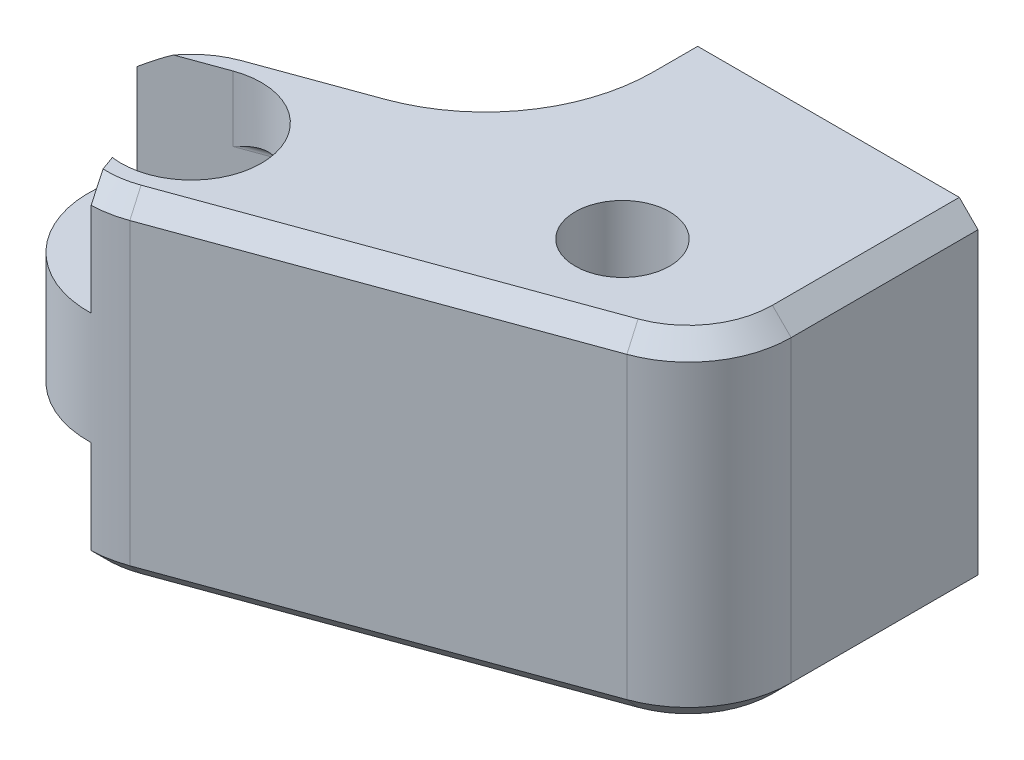
SolidWorks part; units mm, degrees
ref_plane "前视基准面" through (0, 0, 0) normal (0, 0, 1) x (1, 0, 0)
ref_plane "上视基准面" through (0, 0, 0) normal (0, 1, 0) x (1, 0, 0)
ref_plane "右视基准面" through (0, 0, 0) normal (1, 0, 0) x (0, 0, -1)
other "Configuration Table"
ref_plane "基准面1" through (0, 18, 0) normal (0, 1, 0) x (1, 0, 0)
sketch "草图1" plane through (0, 18, 0) normal (0, 1, 0) x (1, 0, 0)
  line L0 (-17.6189, -12.2657) -> (21.6618, 2.0313)
  line L1 (21.6618, 2.0313) -> (-10.5, 2.0313)
  line L2 (-10.5, 2.0313) -> (-21.3811, -1.9291)
  arc A0 (-21.3811, -1.9291) -> (-17.6189, -12.2657) centre (-19.5, -7.0974) ccw
  dimension "D1" = 5.5
  dimension "D2" = 32.1618
  dimension "D3" = 39.2807
  dimension "D4" = 41.1618
extrude "凸台-拉伸1" add sketch "草图1" against normal blind 15
sketch "草图2" plane through (0, 18, 0) normal (0, 1, 0) x (-1, 0, 0)
  line L0 (-21.6618, -2.0313) -> (-5.5, -2.0313)
  line L1 (-5.5, -2.0313) -> (-5.5, 3.8511)
  line L2 (-5.5, 3.8511) -> (-21.6618, -2.0313)
  dimension "D1" = 16.1618
  dimension "D2" = 1.922
  dimension "D3" = 3.9604
extrude "切除-拉伸1" cut sketch "草图2" against normal through all
sketch "草图3" plane through (0, 18, 0) normal (0, 1, 0) x (-1, 0, 0)
  line L0 (20.7826, 3.5736) -> (24.5633, 4.9496)
  line L1 (19.3611, 12.5957) -> (20.0101, 10.8126)
  line L2 (-5.5, -2.0313) -> (-5.5, 3.8511) construction
  line L3 (-5.5, -2.0313) -> (10.5, -2.0313) construction
  arc A0 (20.0101, 10.8126) -> (20.7826, 3.5736) centre (19.5, 7.0974) ccw
  arc A1 (24.5633, 4.9496) -> (19.3611, 12.5957) centre (19.5, 7.0974) ccw
  dimension "D1" = 3.75
  dimension "D2" = 5.5
  dimension "D3" = 24.8611
  dimension "D4" = 25
  dimension "D5" = 25.5101
  dimension "D6" = 26.2826
  dimension "D7" = 5.6049
extrude "切除-拉伸2" cut sketch "草图3" against normal blind 6
ref_plane "基准面2" through (0, 12, 0) normal (0, -1, 0) x (1, 0, 0)
sketch "草图4" plane through (0, 12, 0) normal (0, -1, 0) x (1, 0, 0)
  line L0 (-20.7826, 3.5736) -> (-18.0365, 2.5741)
  line L1 (-18.0365, 2.5741) -> (-17.5577, 3.8896)
  arc A0 (-17.5577, 3.8896) -> (-20.7826, 3.5736) centre (-19.5, 7.0974) cw
  dimension "D1" = 3.75
  dimension "D2" = 1.2826
  dimension "D3" = 2.7461
  dimension "D4" = 3.2249
extrude "切除-拉伸3" cut sketch "草图4" against normal blind 3
sketch "草图5" plane through (0, 3, 0) normal (0, -1, 0) x (1, 0, 0)
  line L0 (-17.2588, 2.291) -> (-16.78, 3.6066)
  line L1 (-16.78, 3.6066) -> (-17.5577, 3.8896)
  line L2 (-20.0101, 10.8126) -> (-19.3611, 12.5957)
  line L3 (-24.5633, 4.9496) -> (-17.2588, 2.291)
  line L4 (5.5, -2.0313) -> (5.5, 3.8511) construction
  arc A0 (-17.5577, 3.8896) -> (-20.0101, 10.8126) centre (-19.5, 7.0974) ccw
  arc A1 (-19.3611, 12.5957) -> (-24.5633, 4.9496) centre (-19.5, 7.0974) ccw
  dimension "D1" = 3.75
  dimension "D2" = 5.5
  dimension "D3" = 22.28
  dimension "D4" = 22.7588
  dimension "D5" = 23.0577
  dimension "D6" = 24.8611
  dimension "D7" = 25
  dimension "D8" = 25.5101
  dimension "D9" = 30.0633
  dimension "D10" = 0.3299
  dimension "D15" = 8.6591
  dimension "D16" = 9.9747
extrude "切除-拉伸4" cut sketch "草图5" against normal blind 3
sketch "草图6" plane through (-15.9762, 0, 5.8149) normal (-0.9397, 0, 0.342) x (0.342, 0, 0.9397)
  line L0 (-2.35, 3) -> (-2.35, 6)
  line L1 (-2.35, 6) -> (-3.75, 6)
  line L2 (-3.75, 6) -> (-3.75, 3)
  line L3 (-3.75, 3) -> (-2.35, 3)
  line L4 (-2.35, 6) -> (-2.35, 3) construction
  line L5 (-3.75, 3) -> (-2.35, 3) construction
  dimension "D1" = 1.4
  dimension "D2" = 3
extrude "切除-拉伸5" cut sketch "草图6" against normal blind 10.5001
sketch "草图7" plane through (-16.7539, 0, 6.0979) normal (-0.9397, 0, 0.342) x (0.342, 0, 0.9397)
  line L0 (-3.75, 12) -> (-2.35, 12)
  line L1 (-2.35, 12) -> (-2.35, 15)
  line L2 (-2.35, 15) -> (-3.75, 15)
  line L3 (-3.75, 15) -> (-3.75, 12)
  line L4 (-2.35, 15) -> (-2.35, 12) construction
  line L5 (-3.75, 12) -> (-2.35, 12) construction
  dimension "D1" = 1.4
  dimension "D2" = 3
extrude "切除-拉伸6" cut sketch "草图7" against normal blind 11.3277
sketch "草图8" plane through (0, 0, -2.0313) normal (0, 0, -1) x (-1, 0, 0)
  line L0 (-5.5, 3) -> (-5.5, 18)
  line L1 (-5.5, 18) -> (10.5, 18)
  line L2 (10.5, 18) -> (10.5, 3)
  line L3 (10.5, 3) -> (-5.5, 3)
  line L4 (-5.5, 3) -> (-5.5, 18) construction
  line L5 (-5.5, 3) -> (10.5, 3) construction
  dimension "D1" = 16
  dimension "D2" = 15
extrude "凸台-拉伸2" add sketch "草图8" along normal blind 7.9687
sketch "草图9" plane through (0, 3, 0) normal (0, -1, 0) x (1, 0, 0)
  line L0 (-17.6189, 12.2657) -> (5.5, 3.8511)
  line L1 (5.5, 3.8511) -> (5.5, -10)
  line L2 (5.5, -10) -> (-10.5, -10)
  line L3 (-10.5, -10) -> (-10.5, -2.0313)
  line L4 (-10.5, -2.0313) -> (-21.3811, 1.9291)
  line L5 (-24.5633, 4.9496) -> (-20.7826, 3.5736)
  line L6 (-20.0101, 10.8126) -> (-19.3611, 12.5957)
  line L7 (-10.5, -10) -> (-10.5, -2.0313) construction
  arc A0 (-19.3611, 12.5957) -> (-17.6189, 12.2657) centre (-19.5, 7.0974) cw
  arc A1 (-21.3811, 1.9291) -> (-24.5633, 4.9496) centre (-19.5, 7.0974) cw
  arc A2 (-20.7826, 3.5736) -> (-20.0101, 10.8126) centre (-19.5, 7.0974) ccw
  dimension "D1" = 5.5
  dimension "D2" = 5.5
  dimension "D3" = 3.75
  dimension "D4" = 16
  dimension "D5" = 7.1189
  dimension "D6" = 8.8611
  dimension "D7" = 9
  dimension "D8" = 9.5101
  dimension "D9" = 10.2826
  dimension "D10" = 10.8811
  dimension "D11" = 3.9604
  dimension "D12" = 11.9291
extrude "凸台-拉伸3" add sketch "草图9" along normal blind 3
hole_wizard "孔1" positions "草图11" profile "草图10" legacy
sketch "草图11" plane through (0, 0, -10) normal (0, 0, -1) x (-1, 0, 0)
  point P0 (4.5, 9)
sketch "草图10" plane through (-4.5, 9, -10) normal (1, 0, 0) x (0, 1, 0)
  line L0 (0, 0) -> (0, 7)
  line L1 (0, 7) -> (2.1, 7)
  line L2 (2.1, 7) -> (2.1, 0)
  line L3 (2.1, 0) -> (0, 0)
  line L4 (0, 110) -> (0, -10) construction
  dimension "直径" = 4.2
  dimension "深度" = 7
hole_wizard "孔2" positions "草图13" profile "草图12" legacy
sketch "草图13" plane through (0, 0, -10) normal (0, 0, -1) x (-1, 0, 0)
  point P0 (-0.5, 13)
sketch "草图12" plane through (0.5, 13, -10) normal (1, 0, 0) x (0, 1, 0)
  line L0 (0, 0) -> (0, 4)
  line L1 (0, 4) -> (1.015, 4)
  line L2 (1.015, 4) -> (1.015, 0)
  line L3 (1.015, 0) -> (0, 0)
  line L4 (0, 110) -> (0, -10) construction
  dimension "直径" = 2.03
  dimension "深度" = 4
hole_wizard "孔3" positions "草图15" profile "草图14" legacy
sketch "草图15" plane through (0, 0, -10) normal (0, 0, -1) x (-1, 0, 0)
  point P0 (-0.5, 5)
sketch "草图14" plane through (0.5, 5, -10) normal (1, 0, 0) x (0, 1, 0)
  line L0 (0, 0) -> (0, 4)
  line L1 (0, 4) -> (1.015, 4)
  line L2 (1.015, 4) -> (1.015, 0)
  line L3 (1.015, 0) -> (0, 0)
  line L4 (0, 110) -> (0, -10) construction
  dimension "直径" = 2.03
  dimension "深度" = 4
hole_wizard "孔4" positions "草图17" profile "草图16" legacy
sketch "草图17" plane through (0, 18, 0) normal (0, 1, 0) x (1, 0, 0)
  point P0 (-2.5855, -0.9411)
sketch "草图16" plane through (-2.5855, 18, 0.9411) normal (1, 0, 0) x (0, 0, 1)
  line L0 (0, 0) -> (0, 18)
  line L1 (0, 18) -> (2.525, 18)
  line L2 (2.525, 18) -> (2.525, 0)
  line L3 (2.525, 0) -> (0, 0)
  line L4 (0, 110) -> (0, -10) construction
  dimension "直径" = 5.05
  dimension "深度" = 18
hole_wizard "孔5" positions "草图19" profile "草图18" legacy
sketch "草图19" plane through (0, 12, 0) normal (0, 1, 0) x (1, 0, 0)
  point P0 (-19.5, -7.0974)
sketch "草图18" plane through (-19.5, 12, 7.0974) normal (1, 0, 0) x (0, 0, 1)
  line L0 (0, 0) -> (0, 12)
  line L1 (0, 12) -> (2.51, 12)
  line L2 (2.51, 12) -> (2.51, 0)
  line L3 (2.51, 0) -> (0, 0)
  line L4 (0, 110) -> (0, -10) construction
  dimension "直径" = 5.02
  dimension "深度" = 12
fillet "圆角1" radius 5.5 1 edges at (5.5, 9, 3.8511) tangent propagation no
fillet "圆角2" radius 8 1 edges at (-10.5, 9, -2.0313) tangent propagation no
chamfer "倒角1" distance 1 angle 45 16 edges at (-10.5, 0, -8.8165) (-23.2864, 0, 3.1083) (-11.9468, 0, -3.0443) (-18.5725, 0, 0.9069) (-18.4766, 0, 12.5014) (5.5, 0, -5) (-7.8689, 0, 8.717) (4.5053, 0, 3.1547) (-23.2864, 18, 3.1083) (-18.5725, 18, 0.9069) (-10.5, 18, -8.8165) (-11.9468, 18, -3.0443) (-18.4766, 18, 12.5014) (5.5, 18, -5) (-7.8689, 18, 8.717) (4.5053, 18, 3.1547)
fillet "圆角3" radius 0.5 7 edges at (-14.0873, 15, 1.1367) (-12.2354, 3, 1.9525) (-14.0873, 3, 1.1367) (-12.2354, 6, 1.9525) (-12.2354, 15, 1.9525) (-15.9776, 6, 1.8247) (-12.2354, 12, 1.9525) tangent propagation no
